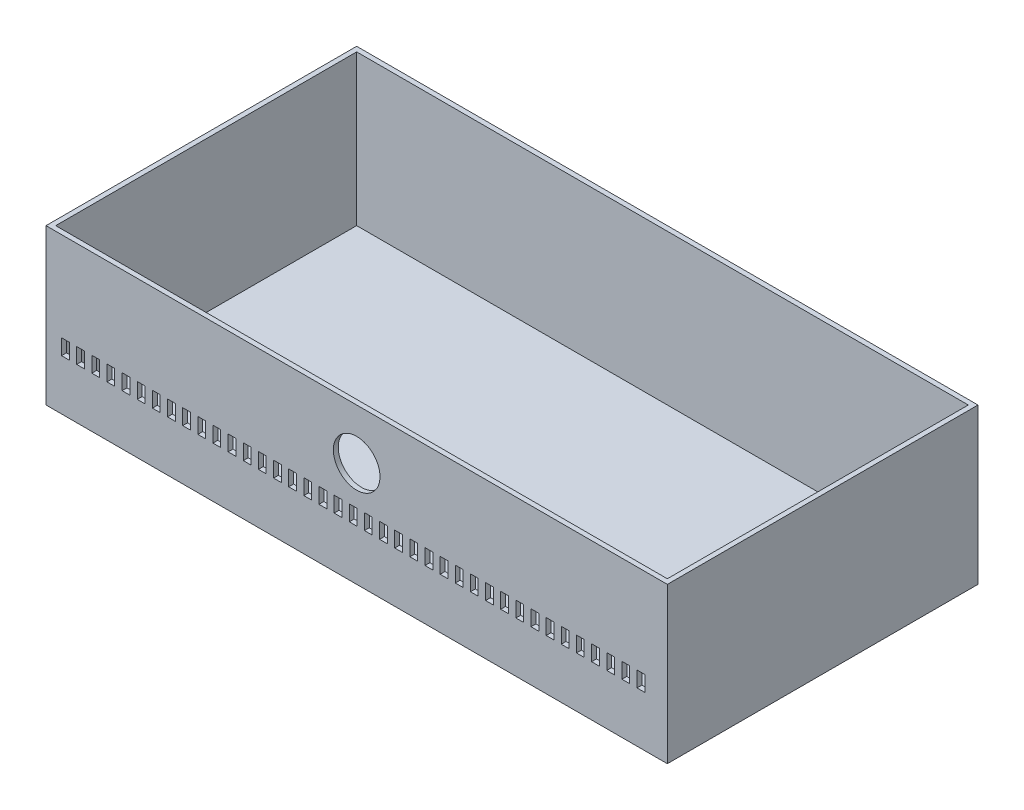
SolidWorks part; units mm, degrees
ref_plane "Front Plane" through (0, 0, 0) normal (0, 0, 1) x (1, 0, 0)
ref_plane "Top Plane" through (0, 0, 0) normal (0, 1, 0) x (1, 0, 0)
ref_plane "Right Plane" through (0, 0, 0) normal (1, 0, 0) x (0, 0, -1)
sketch "Sketch1" plane through (0, 0, 0) normal (0, 1, 0) x (1, 0, 0)
  line L1 (-101.6, -50.8) -> (101.6, -50.8)
  line L2 (-101.6, -50.8) -> (-101.6, 50.8)
  line L3 (-101.6, 50.8) -> (101.6, 50.8)
  line L4 (101.6, -50.8) -> (101.6, 50.8)
  line L5 (-101.6, -50.8) -> (101.6, 50.8) construction
  line L6 (-101.6, 50.8) -> (101.6, -50.8) construction
  point P0 (0, 0)
  dimension "D1" = 203.2
  dimension "D2" = 101.6
extrude "Boss-Extrude1" add sketch "Sketch1" along normal blind 50.8
sketch "Sketch2" plane through (0, 50.8, 0) normal (0, 1, 0) x (1, 0, 0)
  line L0 (-101.6, 50.8) -> (-101.6, -50.8) construction
  line L1 (-100.0125, -49.2125) -> (100.0125, -49.2125)
  line L2 (-100.0125, -49.2125) -> (-100.0125, 49.2125)
  line L3 (-100.0125, 49.2125) -> (100.0125, 49.2125)
  line L4 (100.0125, -49.2125) -> (100.0125, 49.2125)
  line L5 (-100.0125, -49.2125) -> (100.0125, 49.2125) construction
  line L6 (-100.0125, 49.2125) -> (100.0125, -49.2125) construction
  line L7 (101.6, 50.8) -> (-101.6, 50.8) construction
  line L8 (-101.6, -50.8) -> (101.6, -50.8) construction
  point P0 (0, 0)
  dimension "D1" = 1.5875
  dimension "D2" = 1.5875
  dimension "D3" = 1.5875
extrude "Cut-Extrude1" cut sketch "Sketch2" against normal blind 49.2125
sketch "Sketch3" plane through (0, 0, 50.8) normal (0, 0, 1) x (1, 0, 0)
  line L8 (-101.6, 50.8) -> (-101.6, 0) construction
  line L9 (-96.52, 21.59) -> (-93.98, 21.59)
  line L10 (-96.52, 21.59) -> (-96.52, 16.51)
  line L11 (-96.52, 16.51) -> (-93.98, 16.51)
  line L12 (-93.98, 21.59) -> (-93.98, 16.51)
  line L13 (-101.6, 50.8) -> (101.6, 50.8) construction
  dimension "D1" = 5.08
  dimension "D3" = 29.21
  dimension "D5" = 2.54
  dimension "D6" = 5.08
extrude "Cut-Extrude2" cut sketch "Sketch3" against normal blind 7.62
pattern_linear "LPattern1" count 39 spacing 4.953 along (1, 0, 0) of "Cut-Extrude2"
sketch "Sketch4" plane through (0, 0, 50.8) normal (0, 0, 1) x (1, 0, 0)
  line L0 (-101.6, 50.8) -> (101.6, 50.8) construction
  circle A0 centre (0, 34.29) radius 7.62
  dimension "D1" = 15.24
  dimension "D2" = 16.51
extrude "Cut-Extrude3" cut sketch "Sketch4" against normal blind 7.62
sketch "Sketch5" plane through (101.6, 0, 0) normal (1, 0, 0) x (0, 0, -1)
  line L0 (50.8, 50.8) -> (50.8, 0) construction
  line L1 (-50.8, 50.8) -> (50.8, 50.8) construction
  circle A0 centre (38.1, 12.7) radius 8.128
  dimension "D1" = 12.7
  dimension "D2" = 38.1
sketch "Sketch6" plane through (0, 0, -50.8) normal (0, 0, -1) x (-1, 0, 0)
  line L0 (-101.6, 50.8) -> (101.6, 50.8) construction
  line L1 (-101.6, 50.8) -> (-101.6, 0) construction
  circle A0 centre (-88.9, 12.7) radius 8.128
  dimension "D1" = 38.1
  dimension "D2" = 12.7
extrude "Cut-Extrude5" cut sketch "Sketch6" against normal blind 7.62
